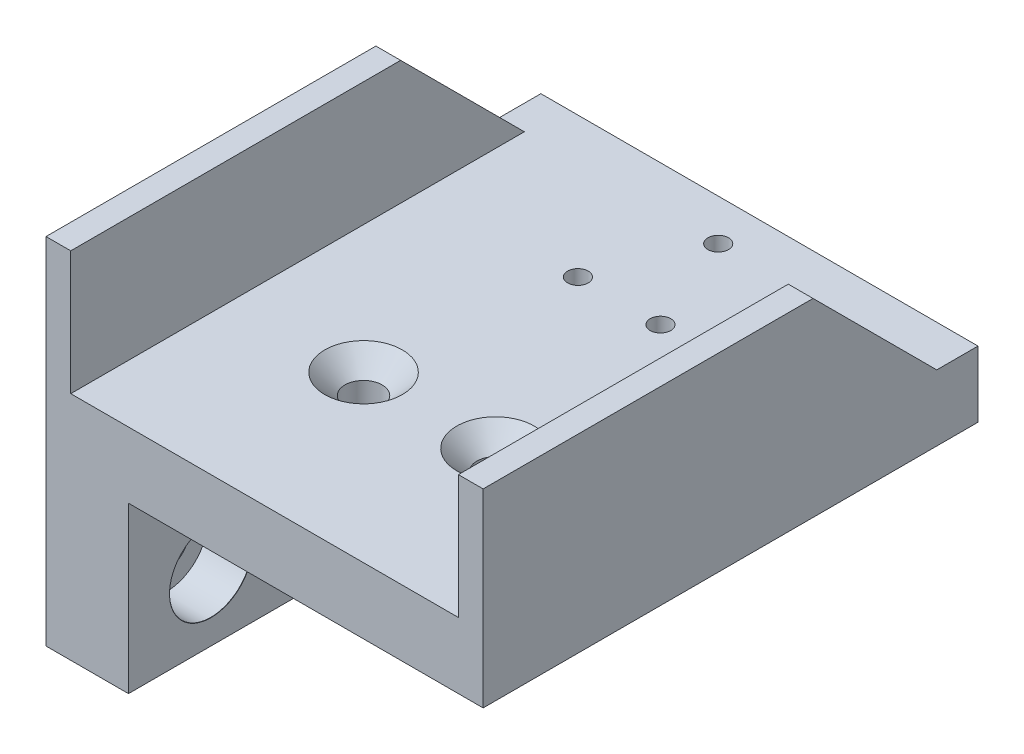
SolidWorks part; units mm, degrees
material "ABS"
ref_plane "Front Plane" through (0, 0, 0) normal (0, 0, 1) x (1, 0, 0)
ref_plane "Top Plane" through (0, 0, 0) normal (0, 1, 0) x (1, 0, 0)
ref_plane "Right Plane" through (0, 0, 0) normal (1, 0, 0) x (0, 0, -1)
sketch "Sketch1" plane through (0, 0, 0) normal (0, 0, 1) x (1, 0, 0)
  line L0 (-23.5, 11.5) -> (-23.5, -3.5)
  line L1 (26.5, -11.5) -> (-26.5, -11.5)
  line L2 (26.5, -11.5) -> (26.5, 11.5)
  line L3 (26.5, 11.5) -> (23.5, 11.5)
  line L4 (-26.5, -11.5) -> (-26.5, 11.5)
  line L5 (26.5, -11.5) -> (-26.5, 11.5) construction
  line L6 (26.5, 11.5) -> (-26.5, -11.5) construction
  line L7 (-23.5, -3.5) -> (23.5, -3.5)
  line L8 (0, -3.5) -> (0, 0) construction
  line L9 (23.5, 11.5) -> (23.5, -3.5)
  line L10 (-23.5, 11.5) -> (-26.5, 11.5)
  point P0 (0, 0)
  dimension "D1" = 3
  dimension "D2" = 47
  dimension "D3" = 15
  dimension "D4" = 8
extrude "Boss-Extrude1" add sketch "Sketch1" along normal mid plane 40
sketch "Sketch2" plane through (0, -3.5, 0) normal (0, 1, 0) x (1, 0, 0)
  line L1 (-26.5, 20) -> (26.5, 20)
  line L2 (-26.5, 20) -> (-26.5, 40)
  line L3 (-26.5, 40) -> (26.5, 40)
  line L4 (26.5, 20) -> (26.5, 40)
  dimension "D1" = 20
extrude "Boss-Extrude2" add sketch "Sketch2" against normal up to surface (8 mm away) up to face at (0, -11.5, 0)
sketch "Sketch11" plane through (-26.5, 0, 0) normal (1, 0, 0) x (0, 0, -1)
  line L1 (-20, -11.5) -> (40, -11.5)
  line L2 (-20, -11.5) -> (-20, -31.5)
  line L3 (-20, -31.5) -> (40, -31.5)
  line L4 (40, -11.5) -> (40, -31.5)
  point P5 (55, -12.5)
  dimension "D1" = 20
extrude "Boss-Extrude3" add sketch "Sketch11" along normal blind 10
hole_wizard "M3 Tapped Hole1" positions "Sketch3" profile "Sketch5" tap size "M3" standard "DIN" end condition up to next
sketch "Sketch3" plane through (0, -3.5, 0) normal (0, 1, 0) x (1, 0, 0)
  line L0 (0, 35) -> (0, 0) construction
  line L2 (26.5, 40) -> (-26.5, 40) construction
  point P0 (0, 35)
  point P2 (-5, 23)
  point P4 (5, 23)
  dimension "D1" = 10
  dimension "D2" = 12
  dimension "D3" = 5
sketch "Sketch5" plane through (0, -3.5, -35) normal (1, 0, 0) x (0, 0, 1)
  line L0 (0, 0) -> (0, 8)
  line L1 (0, 8) -> (1.25, 8)
  line L2 (1.25, 8) -> (1.25, 0)
  line L5 (1.25, 0) -> (0, 0)
  line L11 (0, -6.35) -> (0, 107.95) construction
  dimension "Thru Tap Drill Dia." = 2.5
  dimension "Thru Tap Drill Depth" = 8
hole_wizard "CSK for M4 Countersunk Flat Head Screw1" positions "Sketch7" profile "Sketch9" countersink size "M4" standard "DIN" end condition up to next
sketch "Sketch7" plane through (0, -3.5, 0) normal (0, 1, 0) x (1, 0, 0)
  line L0 (0, 0) -> (0, -20) construction
  line L1 (23.5, -20) -> (-23.5, -20) construction
  line L3 (-23.5, 0) -> (-8, 0) construction
  line L4 (-23.5, -20) -> (-23.5, 20) construction
  point P0 (-8, 0)
  point P10 (8, 0)
  dimension "D1" = 16
sketch "Sketch9" plane through (-8, -3.5, 0) normal (1, 0, 0) x (0, 0, 1)
  line L0 (0, 0) -> (0, 8)
  line L1 (0, 8) -> (2.25, 8)
  line L2 (2.25, 8) -> (2.25, 2.45)
  line L3 (2.25, 2.45) -> (4.7, 0)
  line L5 (4.7, 0) -> (0, 0)
  line L6 (-2.25, 2.45) -> (-4.7, 0) construction
  line L11 (0, -6.35) -> (0, 107.95) construction
  dimension "Thru Hole Dia." = 4.5
  dimension "Thru Hole Depth" = 8
  dimension "Near C'Sink Dia." = 9.4
  dimension "Near C'Sink Angle" = 90
chamfer "Chamfer1" distance 15 angle 45 2 edges at (-25, -3.5, -20) (25, -3.5, -20)
hole_wizard "CBORE for M5 Hex Socket Head Cap Screw1" positions "Sketch12" profile "Sketch14" counterbore size "M5" standard "DIN" end condition up to next
sketch "Sketch12" plane through (-16.5, 0, 0) normal (1, 0, 0) x (0, 0, -1)
  line L0 (10, -23.5) -> (10, -31.5) construction
  line L1 (-20, -31.5) -> (40, -31.5) construction
  line L4 (40, -31.5) -> (40, -11.5) construction
  point P0 (30, -23.5)
  point P5 (10, -23.5)
  point P6 (-10, -23.5)
  point P14 (51.5734, -23.5)
  dimension "D2" = 10
  dimension "D3" = 8
  dimension "D1" = 3
sketch "Sketch14" plane through (-16.5, -23.5, -30) normal (0, 1, 0) x (0, 0, -1)
  line L0 (0, 0) -> (0, 10)
  line L1 (2.75, 9.975) -> (2.775, 10)
  line L2 (5, 5.4) -> (2.75, 5.4)
  line L3 (2.75, 5.4) -> (2.75, 9.975)
  line L5 (5, 5.4) -> (5, 0.025)
  line L6 (5, 0.025) -> (5.025, 0)
  line L7 (5.025, 0) -> (0, 0)
  line L8 (-5, 0.025) -> (-5.025, 0) construction
  line L11 (0, -6.35) -> (0, 107.95) construction
  line L12 (2.775, 10) -> (0, 10)
  line L13 (-2.75, 9.975) -> (-2.775, 10) construction
  dimension "Thru Hole Dia." = 5.5
  dimension "Thru Hole Depth" = 10
  dimension "C'Bore Dia." = 10
  dimension "C'Bore Depth" = 5.4
  dimension "Near C'Sink Dia." = 10.05
  dimension "Near C'Sink Angle" = 90
  dimension "Far C'Sink Dia." = 5.55
  dimension "Far C'Sink Angle" = 90
